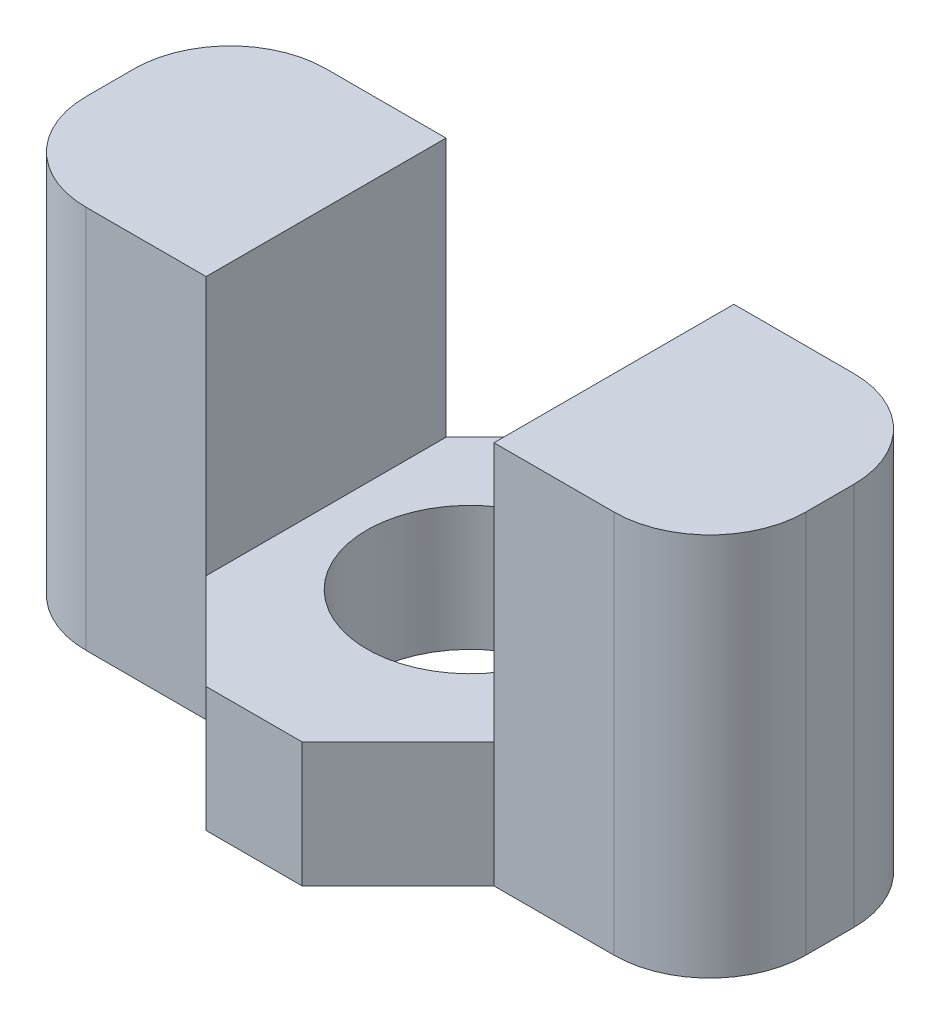
SolidWorks part; units mm, degrees
ref_plane "前视基准面" through (0, 0, 0) normal (0, 0, 1) x (1, 0, 0)
ref_plane "上视基准面" through (0, 0, 0) normal (0, 1, 0) x (1, 0, 0)
ref_plane "右视基准面" through (0, 0, 0) normal (1, 0, 0) x (0, 0, -1)
other "Configuration Table"
sketch "草图1" plane through (0, 0, 0) normal (0, 1, 0) x (1, 0, 0)
  line L0 (-5, 0) -> (5, 0) construction
  line L1 (-7.5, 2.5) -> (7.5, 2.5)
  line L2 (-7.5, 2.5) -> (-7.5, -2.5)
  line L3 (-7.5, -2.5) -> (7.5, -2.5)
  line L4 (7.5, 2.5) -> (7.5, -2.5)
  line L5 (-7.5, 2.5) -> (7.5, -2.5) construction
  line L6 (-7.5, -2.5) -> (7.5, 2.5) construction
  circle A0 centre (5, 0) radius 2.075
  circle A1 centre (-5, 0) radius 2.075
  circle A2 centre (0, 0) radius 2.15
  point P0 (0, 0)
  point P9 (0, 0)
  dimension "D3" = 4.15
  dimension "D5" = 4.3
  dimension "D1" = 15
  dimension "D2" = 5
  dimension "D4" = 10
extrude "凸台-拉伸1" add sketch "草图1" along normal blind 8 contours L4 L1 L2 L3 A2 A1 A0 | A1 | A0 region at (0, 0, -2.3419) region at (5, 0, 0) region at (-5, 0, 0)
extrude "切除-拉伸1" cut sketch "草图1<3>" along normal blind 2 contours A1 | A0 region at (5, 0, 0) region at (-5, 0, 0)
sketch "草图1<3>" plane through (0, 0, 0) normal (0, 1, 0) x (1, 0, 0) same geometry as "草图1"
sketch "草图2" plane through (0, 0, 0) normal (0, 0, 1) x (1, 0, 0)
  line L0 (0, 0) -> (0, 50000) construction
  line L1 (-7.5, 0) -> (7.5, 0) construction
  line L2 (-3, 2.6) -> (3, 2.6)
  line L3 (3, 2.6) -> (3, 8)
  line L4 (-7.5, 8) -> (7.5, 8) construction
  line L5 (3, 8) -> (-3, 8)
  line L6 (0, 8) -> (0, 2.6)
  line L7 (-3, 2.6) -> (-3, 8)
  point P4 (0, 0)
  dimension "D1" = 2.6
  dimension "D2" = 6
  dimension "D3" = 90
extrude "切除-拉伸2" cut sketch "草图2" against normal through all and the other way through all contours L7 L2 L6 L5 | L5 L6 L2 L3 region at (-1.5, 5.3, 0) region at (1.5, 5.3, 0)
sketch "草图3" plane through (0, 0, 0) normal (0, 1, 0) x (1, 0, 0)
  line L0 (0, 0) -> (0, 50000) construction
  line L1 (-3, 2.5) -> (3, 2.5)
  line L2 (-3, 2.5) -> (3, 2.5) construction
  line L4 (3, 2.5) -> (1, 4.5)
  line L5 (1, 4.5) -> (-1, 4.5)
  line L6 (0, 4.5) -> (0, 2.5)
  line L7 (0, 0) -> (50000, 0) construction
  line L8 (-3, 2.5) -> (-1, 4.5)
  line L9 (-3, -2.5) -> (-1, -4.5)
  line L10 (0, -4.5) -> (0, -2.5)
  line L11 (1, -4.5) -> (-1, -4.5)
  line L12 (3, -2.5) -> (1, -4.5)
  line L13 (-3, -2.5) -> (3, -2.5)
  dimension "D1" = 2
  dimension "D2" = 45
  dimension "D3" = 3
extrude "凸台-拉伸2" add sketch "草图3" along normal up to surface (2.6 mm away) contours L8 L1 L6 L5 | L5 L6 L1 L4 | L13 L10 L11 L12 | L13 L9 L11 L10 region at (-1.0833, 0, -3.3333) region at (1.0833, 0, -3.3333) region at (-1.0833, 0, 3.3333) region at (1.0833, 0, 3.3333) up to face at (0, 2.6, -2.15)
fillet "圆角1" radius 2 4 edges at (-7.5, 4, -2.5) (7.5, 4, -2.5) (7.5, 4, 2.5) (-7.5, 4, 2.5)
